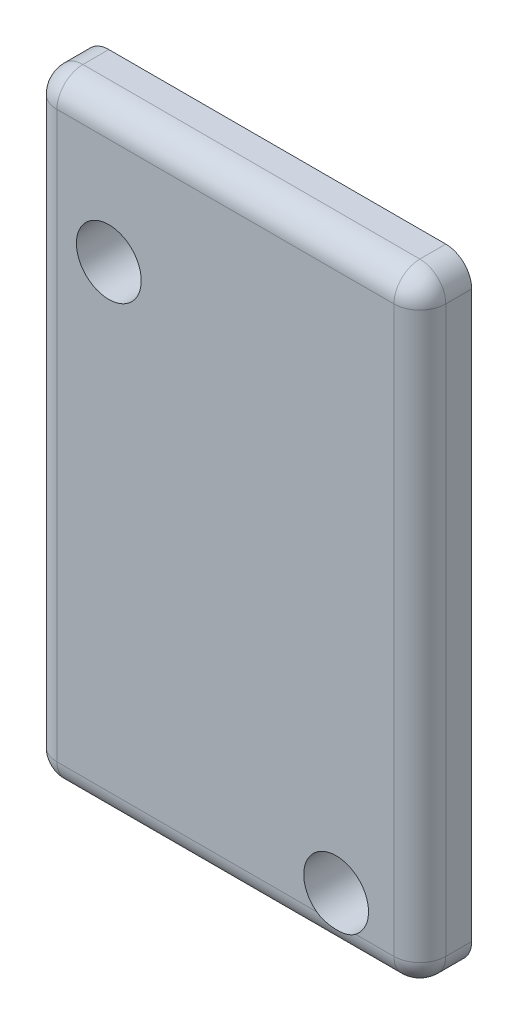
SolidWorks part; units mm, degrees
ref_plane "Piano frontale" through (0, 0, 0) normal (0, 0, 1) x (1, 0, 0)
ref_plane "Piano superiore" through (0, 0, 0) normal (0, 1, 0) x (1, 0, 0)
ref_plane "Piano destro" through (0, 0, 0) normal (1, 0, 0) x (0, 0, -1)
sketch "Schizzo1" plane through (0, 0, 0) normal (0, 0, 1) x (1, 0, 0)
  line L1 (0, 0) -> (-15, 0)
  line L2 (0, 0) -> (0, -23.8)
  line L3 (0, -23.8) -> (-15, -23.8)
  line L4 (-15, 0) -> (-15, -23.8)
  circle A0 centre (-12, -5.1) radius 1.25
  circle A1 centre (-3.23, -21.8) radius 1.25
  dimension "D5" = 2.5
  dimension "D6" = 2.5
  dimension "D1" = 21.8
  dimension "D2" = 5.1
  dimension "D3" = 3.23
  dimension "D4" = 12
  dimension "D7" = 15
  dimension "D8" = 23.8
extrude "Estrusione-Estrusione1" add sketch "Schizzo1" along normal blind 2
fillet "Raccordo1" radius 1 4 edges at (-15, -23.8, 1) (0, -23.8, 1) (0, 0, 1) (-15, 0, 1)
fillet "Raccordo2" radius 1 8 edges at (-14.7071, -0.2929, 2) (-7.5, 0, 2) (-0.2929, -0.2929, 2) (0, -11.9, 2) (-0.2929, -23.5071, 2) (-7.5, -23.8, 2) (-14.7071, -23.5071, 2) (-15, -11.9, 2)
